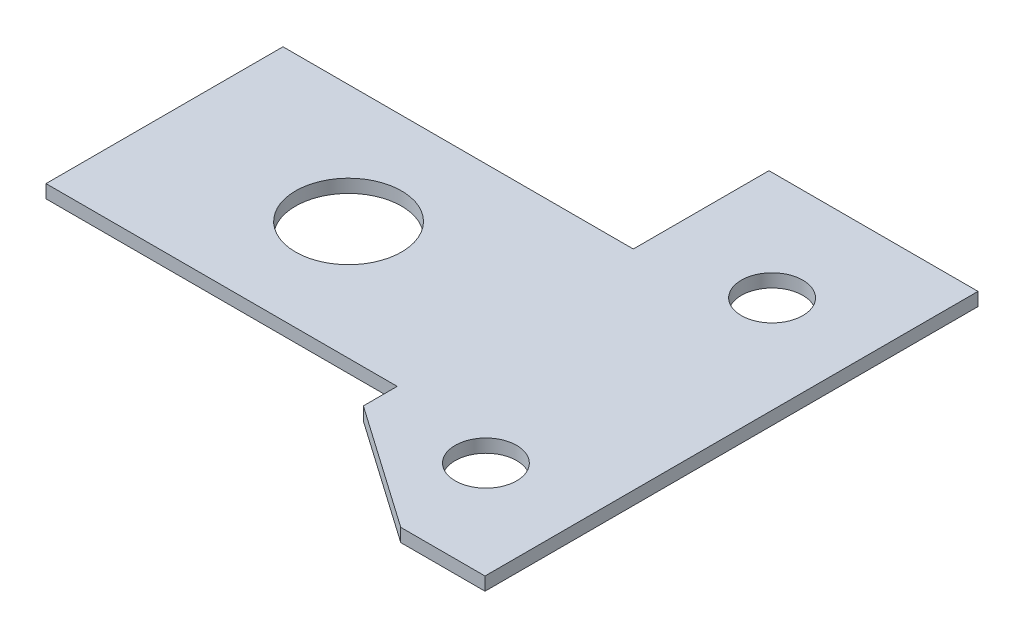
SolidWorks part; units mm, degrees
note: The reader was unsure of these and kept them because the rebuilt part matched: thickness of "Base-Flange1", "Sheet-Metal1", "Sheet-Metal2", "Sheet-Metal3", "Sheet-Metal4".
ref_plane "Front Plane" through (0, 0, 0) normal (0, 0, 1) x (1, 0, 0)
ref_plane "Top Plane" through (0, 0, 0) normal (0, 1, 0) x (1, 0, 0)
ref_plane "Right Plane" through (0, 0, 0) normal (1, 0, 0) x (0, 0, -1)
sketch "Sketch1" plane through (0, 0, 0) normal (0, 1, 0) x (1, 0, 0)
  line L0 (27, 0) -> (27, -9.25)
  line L1 (0, 0) -> (27, 0)
  line L2 (0, 0) -> (0, 18.22)
  line L4 (43, -1.78) -> (43, 18.22)
  line L5 (27, -9.25) -> (43, -9.25)
  line L6 (43, -9.25) -> (43, -1.78)
  line L8 (43, 28.65) -> (43, 18.22)
  line L10 (26.93, 18.22) -> (26.93, 28.65)
  line L11 (43, 28.65) -> (26.93, 28.65)
  line L12 (26.93, 18.22) -> (0, 18.22)
  dimension "D1" = 43
  dimension "D2" = 18.22
  dimension "D3" = 9.25
  dimension "D4" = 27
  dimension "D5" = 16.07
base flange "Base-Flange1" sketch "Sketch1" thickness 1.016 reverse thickness direction no parameters "D1"=0.7366
sketch "Sketch6" plane through (0, 0, 0) normal (0, 1, 0) x (1, 0, 0)
  line L0 (0, 18.22) -> (0, 0) construction
  line L1 (0, 0) -> (27, 0) construction
  circle A0 centre (14.15, 9.11) radius 4.075
  dimension "D1" = 8.15
  dimension "D3" = 9.11
  dimension "D2" = 14.15
extrude "Cut-Extrude1" cut sketch "Sketch6" against normal through all normal cut yes
sketch "Sketch7" plane through (0, 0, 0) normal (0, 1, 0) x (1, 0, 0)
  line L0 (36.5223, -9.25) -> (27, -2.5997)
  line L1 (27, -9.25) -> (43, -9.25) construction
  line L2 (27, 0) -> (27, -9.25) construction
  line L3 (27, -2.5997) -> (27, -9.25)
  line L4 (27, -9.25) -> (36.5223, -9.25)
  dimension "D1" = 11.6147
  dimension "D2" = 6.6503
extrude "Cut-Extrude2" cut sketch "Sketch7" against normal up to next normal cut yes
sketch "Sketch8" plane through (0, 0, 0) normal (0, 1, 0) x (1, 0, 0)
  circle A0 centre (35.5182, -1.698) radius 2.363
  circle A1 centre (35.5182, 20.302) radius 2.363
  circle A2 centre (35.5182, -1.698) radius 2.363 construction
  circle A3 centre (35.5182, 20.302) radius 2.363 construction
extrude "Cut-Extrude3" cut sketch "Sketch8" against normal up to next normal cut yes
sketch "Bend-Lines1" [suppressed] plane through (0, 0, 0) normal (0, 1, 0) x (1, 0, 0)
sketch "Bounding-Box1" [suppressed] plane through (0, 0, 0) normal (0, 1, 0) x (1, 0, 0)
sheet metal parameters "Sheet-Metal1" thickness 1.016 parameters "D1"=0.7366, "D7"=0.0625
flat pattern "Flat-Pattern1" [suppressed]
sketch "Bend-Lines2" plane through (0, 0, 0) normal (0, 1, 0) x (1, 0, 0)
sketch3d "Bounding-Box2" [suppressed]
  line L0 (43, -9.25, 0) -> (0, -9.25, 0) construction
  line L1 (43, 28.65, 0) -> (0, 28.65, 0) construction
  line L2 (43, -9.25, 0) -> (43, 28.65, 0) construction
  line L3 (0, -9.25, 0) -> (0, 28.65, 0) construction
sheet metal parameters "Sheet-Metal2" thickness 1.016 parameters "D1"=0.7366, "D7"=0.0625
flat pattern "Flat-Pattern1"
sketch "Bend-Lines2" plane through (0, 0, 0) normal (0, 1, 0) x (1, 0, 0)
sketch3d "Bounding-Box2" [suppressed]
  line L0 (43, -9.25, 0) -> (0, -9.25, 0) construction
  line L1 (43, 28.65, 0) -> (0, 28.65, 0) construction
  line L2 (43, -9.25, 0) -> (43, 28.65, 0) construction
  line L3 (0, -9.25, 0) -> (0, 28.65, 0) construction
sheet metal parameters "Sheet-Metal3" thickness 1.016 parameters "D1"=0.7366, "D7"=0.0625
flat pattern "Flat-Pattern1"
sketch "Bend-Lines2" plane through (0, 0, 0) normal (0, 1, 0) x (1, 0, 0)
sketch3d "Bounding-Box2" [suppressed]
  line L0 (43, -9.25, 0) -> (0, -9.25, 0) construction
  line L1 (43, 28.65, 0) -> (0, 28.65, 0) construction
  line L2 (43, -9.25, 0) -> (43, 28.65, 0) construction
  line L3 (0, -9.25, 0) -> (0, 28.65, 0) construction
sheet metal parameters "Sheet-Metal4" thickness 1.016 parameters "D1"=0.7366, "D7"=0.0625
flat pattern "Flat-Pattern1"
sketch "Bend-Lines2" plane through (0, 0, 0) normal (0, 1, 0) x (1, 0, 0)
sketch3d "Bounding-Box2" [suppressed]
  line L0 (43, -9.25, 0) -> (0, -9.25, 0) construction
  line L1 (43, 28.65, 0) -> (0, 28.65, 0) construction
  line L2 (43, -9.25, 0) -> (43, 28.65, 0) construction
  line L3 (0, -9.25, 0) -> (0, 28.65, 0) construction
